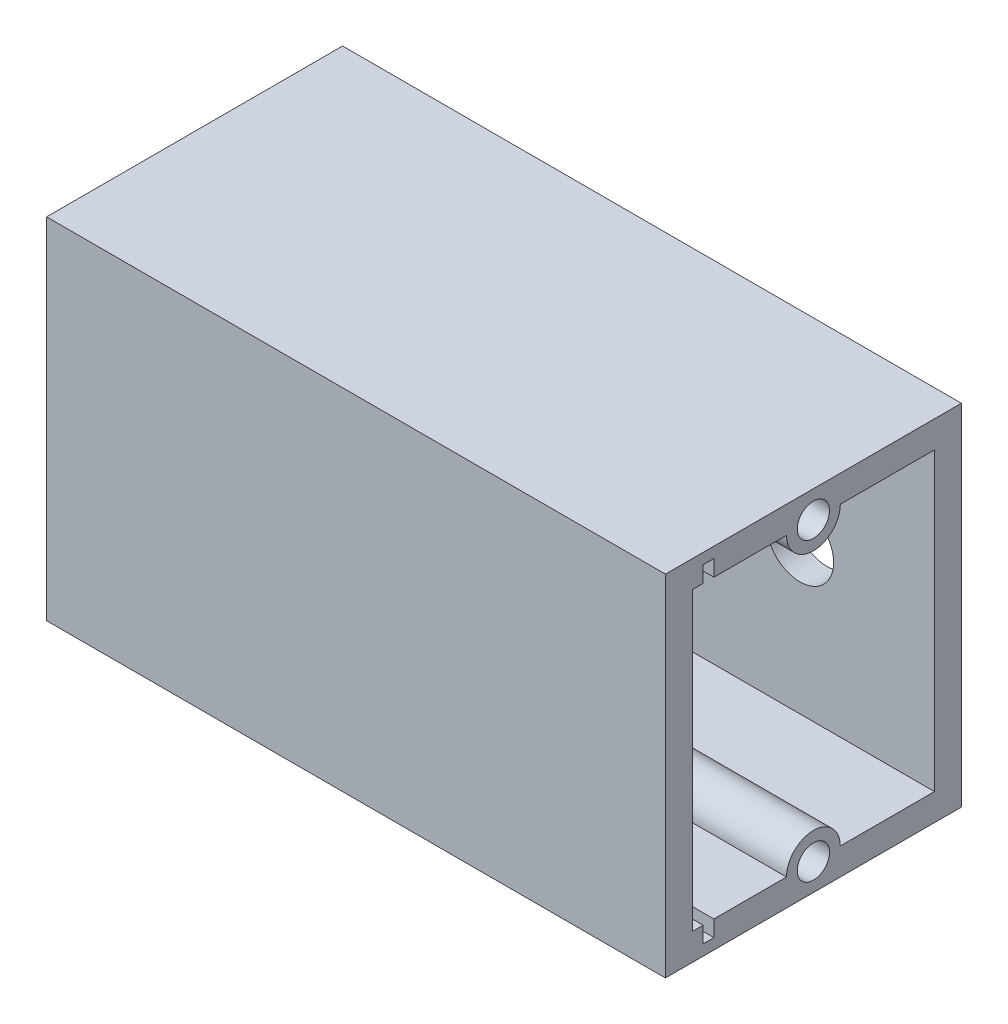
SolidWorks part; units mm, degrees
ref_plane "Plan de face" through (0, 0, 0) normal (0, 0, 1) x (1, 0, 0)
ref_plane "Plan de dessus" through (0, 0, 0) normal (0, 1, 0) x (1, 0, 0)
ref_plane "Plan de droite" through (0, 0, 0) normal (1, 0, 0) x (0, 0, -1)
sketch "Esquisse1" plane through (0, 0, 0) normal (0, 0, 1) x (1, 0, 0)
  line L0 (0, 32.5) -> (120, 32.5) construction
  line L1 (0, 0) -> (120, 0)
  line L2 (0, 0) -> (0, 65)
  line L3 (0, 65) -> (120, 65)
  line L4 (120, 0) -> (120, 65)
  line L5 (60, 65) -> (60, 0) construction
  line L6 (60, 32.5) -> (0, 32.5) construction
  line L7 (0, 32.5) -> (30, 32.5) construction
  line L8 (30, 32.5) -> (30, 65) construction
  line L9 (30, 65) -> (30, 0) construction
  line L10 (30, 0) -> (60, 0) construction
  line L11 (60, 0) -> (120, 0) construction
  line L12 (90, 0) -> (90, 65) construction
  circle A0 centre (30, 32.5) radius 6.25
  circle A1 centre (90, 32.5) radius 6.25
  dimension "D3" = 12.5
  dimension "D4" = 12.5
  dimension "D1" = 120
  dimension "D2" = 65
extrude "Boss.-Extru.1" add sketch "Esquisse1" along normal blind 5
sketch "Esquisse2" plane through (0, 0, 5) normal (0, 0, 1) x (1, 0, 0)
  line L0 (0, 65) -> (5, 65) construction
  line L1 (120, 65) -> (0, 65) construction
  line L2 (0, 65) -> (0, 60) construction
  line L3 (0, 65) -> (0, 0) construction
  line L4 (0, 60) -> (120, 60) construction
  line L5 (120, 0) -> (120, 65) construction
  line L6 (5, 65) -> (5, 0) construction
  line L7 (0, 0) -> (120, 0) construction
  line L8 (120, 0) -> (120, 5) construction
  line L9 (120, 0) -> (115, 0) construction
  line L10 (115, 0) -> (115, 65) construction
  line L11 (120, 5) -> (0, 5) construction
  line L12 (5, 60) -> (115, 60)
  line L13 (115, 60) -> (115, 5)
  line L14 (115, 5) -> (5, 5)
  line L15 (5, 5) -> (5, 60)
  line L17 (0, 65) -> (120, 65)
  line L18 (0, 65) -> (0, 0)
  line L19 (0, 0) -> (120, 0)
  line L20 (120, 65) -> (120, 0)
  line L21 (5, 60) -> (115, 60)
  line L22 (5, 60) -> (5, 5)
  line L23 (5, 5) -> (115, 5)
  line L24 (115, 60) -> (115, 5)
  line L25 (120, 0) -> (0, 0)
  line L26 (120, 0) -> (120, 65)
  line L27 (120, 65) -> (0, 65)
  line L28 (0, 0) -> (0, 65)
  line M13 (0, 65) -> (0, 0)
  line M14 (0, 0) -> (120, 0)
  line M15 (120, 0) -> (120, 65)
  line M16 (120, 65) -> (0, 65)
  dimension "D1" = 5
  dimension "D2" = 5
  dimension "D3" = 5
  dimension "D4" = 5
extrude "Boss.-Extru.3" add sketch "Esquisse2" along normal blind 45 contours L14 L15 L12 L13 M16 M13 M14 M15 region at (60, 63.6353, 5)
sketch "Esquisse4" plane through (0, 0, 50) normal (0, 0, 1) x (1, 0, 0)
  line L1 (0, 65) -> (120, 65)
  line L2 (0, 65) -> (0, 0)
  line L3 (0, 0) -> (120, 0)
  line L4 (120, 65) -> (120, 0)
extrude "Boss.-Extru.4" add sketch "Esquisse4" along normal blind 5
sketch "Esquisse5" plane through (120, 0, 0) normal (1, 0, 0) x (0, 0, -1)
  line L1 (-55, 65) -> (0, 65)
  line L2 (-55, 65) -> (-55, 0)
  line L3 (-55, 0) -> (0, 0)
  line L4 (0, 65) -> (0, 0)
extrude "Enlèv. mat.-Extru.1" cut sketch "Esquisse5" against normal blind 5
sketch "Esquisse6" plane through (115, 0, 0) normal (1, 0, 0) x (0, 0, -1)
  line L0 (0, 65) -> (-55, 65) construction
  line L1 (-48, 63) -> (-46, 63)
  line L2 (-48, 63) -> (-48, 2)
  line L3 (-48, 2) -> (-46, 2)
  line L4 (-46, 63) -> (-46, 2)
  line L5 (-55, 0) -> (0, 0) construction
  line L6 (-50, 60) -> (-50, 5) construction
  dimension "D1" = 2
  dimension "D2" = 2
  dimension "D3" = 2
  dimension "D4" = 2
extrude "Enlèv. mat.-Extru.2" cut sketch "Esquisse6" against normal blind 62.25
sketch "Esquisse7" plane through (115, 0, 0) normal (1, 0, 0) x (0, 0, -1)
  line L0 (0, 65) -> (-55, 65) construction
  line L1 (-55, 65) -> (-27.5, 65) construction
  line L2 (-27.5, 65) -> (-27.5, 0) construction
  line L3 (-55, 0) -> (0, 0) construction
  line L4 (-46, 60) -> (-5, 60) construction
  line L5 (-50, 60) -> (-5, 60) construction
  line L6 (0, 32.5) -> (-55, 32.5) construction
  line L7 (0, 0) -> (0, 65) construction
  line L8 (-55, 65) -> (-55, 0) construction
  line L9 (-22.5, 60) -> (-32.5, 60)
  line L10 (-32.5, 5) -> (-22.5, 5)
  arc A0 (-22.5, 60) -> (-32.5, 60) centre (-27.5, 60) cw
  arc A1 (-22.5, 5) -> (-32.5, 5) centre (-27.5, 5) ccw
  dimension "D1" = 5
extrude "Boss.-Extru.6" add sketch "Esquisse7" against normal up to surface (110 mm away) contours L9 A0 | L10 A1 up to face at (5, 32.5, 27.5)
sketch "Esquisse8" plane through (115, 0, 0) normal (1, 0, 0) x (0, 0, -1)
  line L0 (-5, 60) -> (-50, 60) construction
  line L1 (-50, 60) -> (-50, 5) construction
  line L2 (-50, 5) -> (-5, 5) construction
  line L3 (-5, 5) -> (-5, 60) construction
  line L4 (-5, 60) -> (-27.5, 60) construction
  line L5 (-27.5, 60) -> (-27.5, 5) construction
  circle A0 centre (-27.5, 60) radius 3
  circle A1 centre (-27.5, 5) radius 3
  dimension "D1" = 6
  dimension "D2" = 6
extrude "Enlèv. mat.-Extru.3" cut sketch "Esquisse8" against normal blind 12
sketch "Esquisse9" plane through (115, 0, 0) normal (1, 0, 0) x (0, 0, -1)
  line L0 (-48, 2) -> (-48, 63) construction
  line L1 (-32.5, 60) -> (-50, 60) construction
